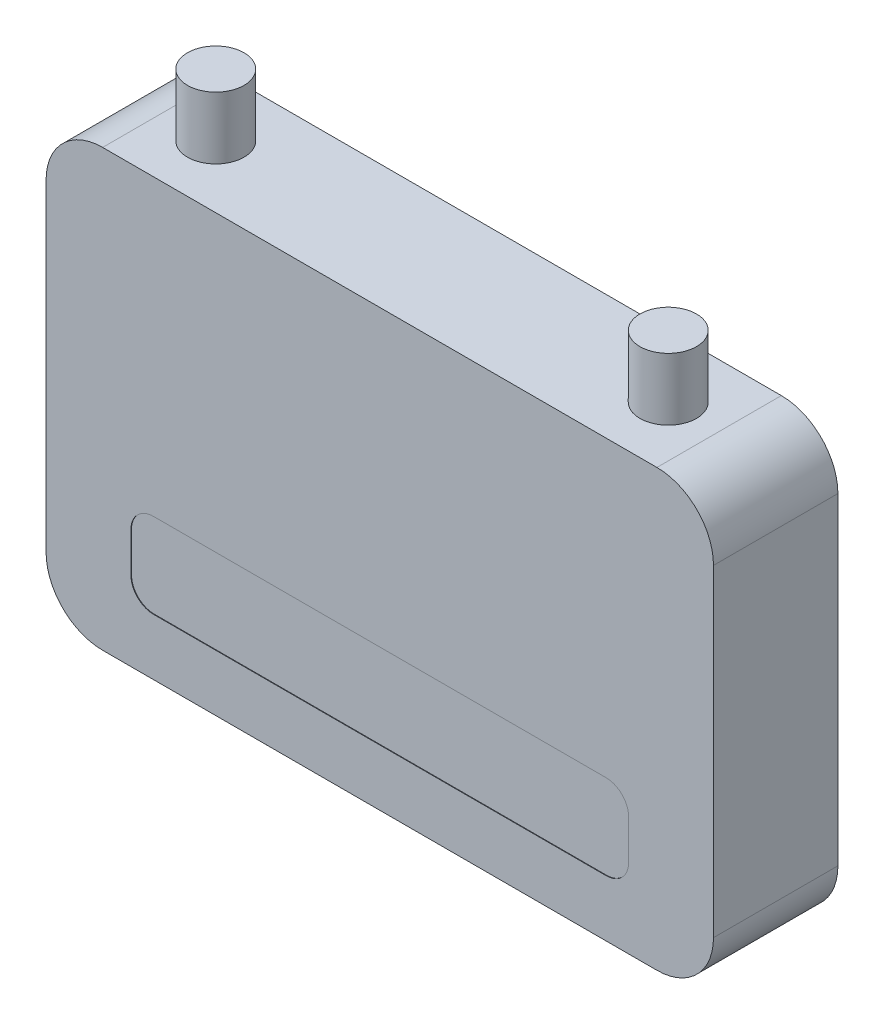
SolidWorks part; units mm, degrees
ref_plane "Front Plane" through (0, 0, 0) normal (0, 0, 1) x (1, 0, 0)
ref_plane "Top Plane" through (0, 0, 0) normal (0, 1, 0) x (1, 0, 0)
ref_plane "Right Plane" through (0, 0, 0) normal (1, 0, 0) x (0, 0, -1)
sketch "Sketch1" plane through (0, 0, 0) normal (0, 0, 1) x (1, 0, 0)
  line L1 (-49, -38.5) -> (49, -38.5)
  line L2 (-59, -28.5) -> (-59, 28.5)
  line L3 (-49, 38.5) -> (49, 38.5)
  line L4 (59, -28.5) -> (59, 28.5)
  line L5 (-59, -38.5) -> (59, 38.5) construction
  line L6 (-59, 38.5) -> (59, -38.5) construction
  arc A0 (49, 38.5) -> (59, 28.5) centre (49, 28.5) cw
  arc A1 (49, -38.5) -> (59, -28.5) centre (49, -28.5) ccw
  arc A2 (-49, -38.5) -> (-59, -28.5) centre (-49, -28.5) cw
  arc A3 (-59, 28.5) -> (-49, 38.5) centre (-49, 28.5) cw
  point P0 (0, 0)
  dimension "D3" = 10
  dimension "D1" = 118
  dimension "D2" = 77
extrude "Boss-Extrude1" add sketch "Sketch1" along normal mid plane 22
sketch "Sketch2" plane through (0, 38.5, 0) normal (0, 1, 0) x (1, 0, 0)
  line L0 (-40, 0) -> (40, 0) construction
  circle A0 centre (-40, 0) radius 5
  circle A1 centre (40, 0) radius 5
  point P4 (0, 0)
  point P5 (0, 0)
  dimension "D2" = 10
  dimension "D1" = 80
extrude "Boss-Extrude2" add sketch "Sketch2" along normal mid plane 22
sketch "Sketch3" plane through (0, 0, -11) normal (0, 0, -1) x (-1, 0, 0)
  line L1 (-48, -31) -> (48, -31) construction
  line L2 (-48, -31) -> (-48, 31) construction
  line L3 (-48, 31) -> (48, 31) construction
  line L4 (48, -31) -> (48, 31) construction
  line L5 (-48, -31) -> (48, 31) construction
  line L6 (-48, 31) -> (48, -31) construction
  circle A0 centre (-48, 31) radius 3.25
  circle A1 centre (-48, -31) radius 3.25
  circle A2 centre (48, -31) radius 3.25
  circle A3 centre (48, 31) radius 3.25
  point P0 (0, 0)
  dimension "D3" = 6.5
  dimension "D1" = 96
  dimension "D2" = 62
extrude "Boss-Extrude3" add sketch "Sketch3" along normal mid plane 2
fillet "Fillet1" radius 2 4 edges at (-51.25, -31, -12) (44.75, -31, -12) (-51.25, 31, -12) (44.75, 31, -12)
sketch "Sketch4" plane through (0, 0, 11) normal (0, 0, 1) x (1, 0, 0)
  line L0 (0, 0) -> (0, -21) construction
  line L1 (-49, -38.5) -> (49, -38.5) construction
  line L2 (-40, -28.5) -> (40, -28.5)
  line L3 (-44, -24.5) -> (-44, -17.5)
  line L4 (-40, -13.5) -> (40, -13.5)
  line L5 (44, -24.5) -> (44, -17.5)
  line L6 (-44, -28.5) -> (44, -13.5) construction
  line L7 (-44, -13.5) -> (44, -28.5) construction
  arc A0 (40, -13.5) -> (44, -17.5) centre (40, -17.5) cw
  arc A1 (40, -28.5) -> (44, -24.5) centre (40, -24.5) ccw
  arc A2 (-40, -28.5) -> (-44, -24.5) centre (-40, -24.5) cw
  arc A3 (-44, -17.5) -> (-40, -13.5) centre (-40, -17.5) cw
  dimension "D4" = 4
  dimension "D1" = 15
  dimension "D2" = 88
  dimension "D3" = 10
extrude "Cut-Extrude1" cut sketch "Sketch4" against normal blind 0.1
